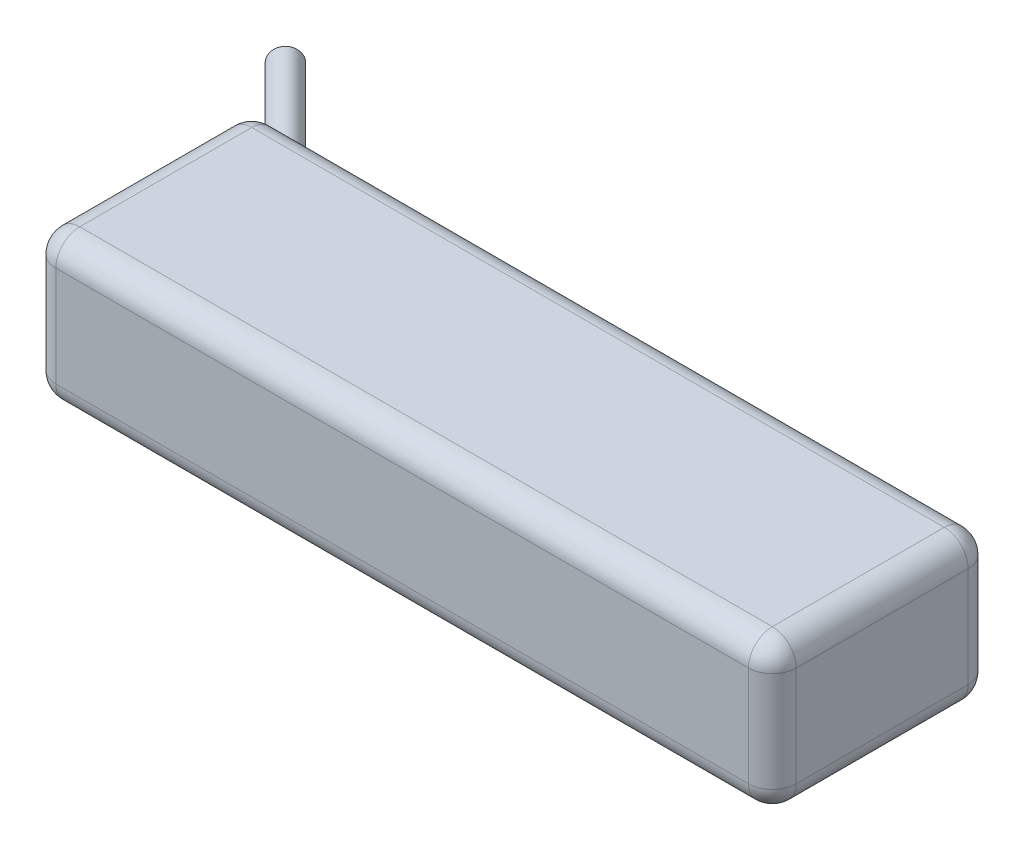
SolidWorks part; units mm, degrees
ref_plane "Front Plane" through (0, 0, 0) normal (0, 0, 1) x (1, 0, 0)
ref_plane "Top Plane" through (0, 0, 0) normal (0, 1, 0) x (1, 0, 0)
ref_plane "Right Plane" through (0, 0, 0) normal (1, 0, 0) x (0, 0, -1)
ref_axis "X" through (-88.99, 0, 0) along (1, 0, 0)
ref_axis "Y" through (0, 55, 0) along (0, -1, 0)
ref_axis "Z" through (0, 0, -88.99) along (0, 0, 1)
sketch "Sketch1" plane through (0, 0, 0) normal (0, 1, 0) x (1, 0, 0)
  line L1 (-77.5, 23) -> (77.5, 23)
  line L2 (-77.5, 23) -> (-77.5, -23)
  line L3 (-77.5, -23) -> (77.5, -23)
  line L4 (77.5, 23) -> (77.5, -23)
  line L5 (-77.5, 23) -> (77.5, -23) construction
  line L6 (-77.5, -23) -> (77.5, 23) construction
  point P0 (0, 0)
  dimension "D1" = 46
  dimension "D2" = 155
extrude "Boss-Extrude1" add sketch "Sketch1" along normal mid plane 31
sketch "Sketch3" plane through (0, 0, 0) normal (0, 1, 0) x (1, 0, 0)
  line L0 (-77.5, 23) -> (-77.5, 13)
  line L1 (-77.5, 13) -> (-67.5, 23)
  line L2 (-67.5, 23) -> (-77.5, 23)
  line L3 (-77.5, 23) -> (-72.5, 18) construction
  point P2 (-72.5, 18)
  dimension "D1" = 45
  dimension "D2" = 10
ref_plane "Plane1" through (-45.25, 0, -45.25) normal (0.7071, 0, 0.7071) x (0.7071, 0, -0.7071)
sketch "Sketch4" plane through (-45.25, 0, -45.25) normal (0.7071, 0, 0.7071) x (0.7071, 0, -0.7071)
  line L0 (-33.5373, 6) -> (-33.5373, -6) construction
  line L1 (0, 0) -> (-33.5373, 0) construction
  line L2 (-38.5373, 15.5) -> (-38.5373, -15.5) construction
  circle A0 centre (-33.5373, 6) radius 3
  circle A1 centre (-33.5373, -6) radius 3
  point P7 (-33.9561, 6)
  dimension "D1" = 6
  dimension "D2" = 6
  dimension "D3" = 12
  dimension "D4" = 5
extrude "Boss-Extrude2" add sketch "Sketch4" against normal blind 30
fillet "Fillet1" radius 5 12 edges at (77.5, 0, -23) (-77.5, 0, -23) (-77.5, 0, 23) (77.5, 0, 23) (0, -15.5, -23) (-77.5, -15.5, 0) (0, -15.5, 23) (77.5, -15.5, 0) (0, 15.5, 23) (-77.5, 15.5, 0) (0, 15.5, -23) (77.5, 15.5, 0)
